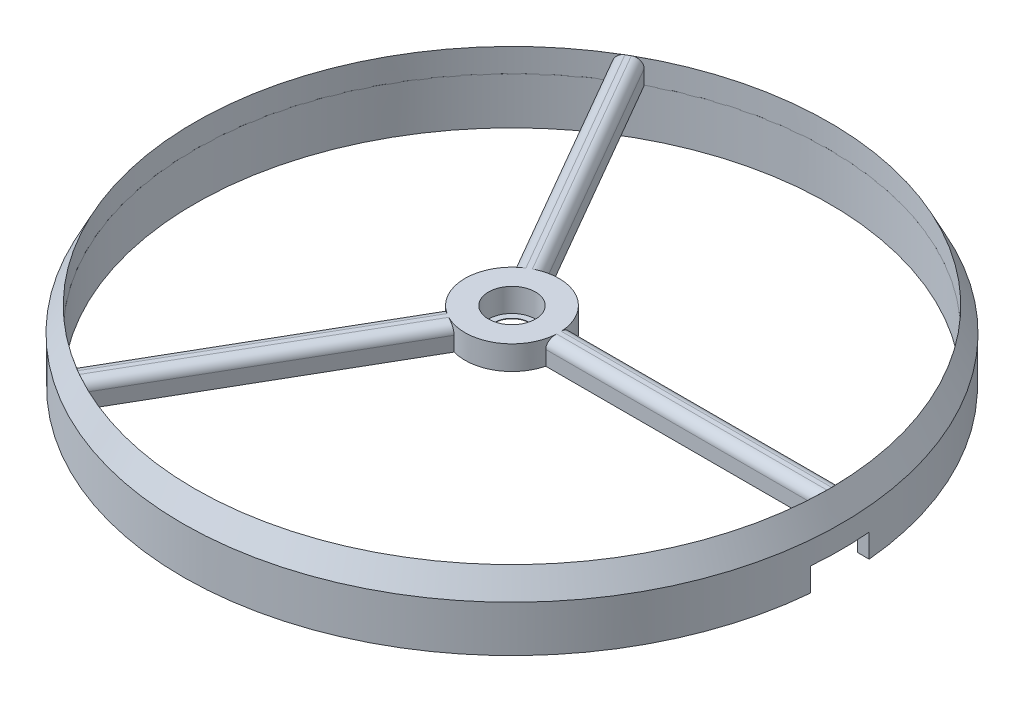
SolidWorks part; units mm, degrees
material "PET"
ref_plane "Front Plane" through (0, 0, 0) normal (0, 0, 1) x (1, 0, 0)
ref_plane "Top Plane" through (0, 0, 0) normal (0, 1, 0) x (1, 0, 0)
ref_plane "Right Plane" through (0, 0, 0) normal (1, 0, 0) x (0, 0, -1)
ref_axis "X-Axis" through (-48.9639, 0, 0) along (1, 0, 0)
ref_axis "Y-Axis" through (0, 10.0012, 0) along (0, -1, 0)
ref_axis "Z-Axis" through (0, 0, -48.9639) along (0, 0, 1)
sketch "Sketch1" plane through (0, 0, 0) normal (0, 1, 0) x (1, 0, 0)
  circle A0 centre (0, 0) radius 44.45
  dimension "D1" = 88.9
extrude "Extrude-Thin1" add sketch "Sketch1" along normal blind 6.35 thin thin type one direction reverse wall 1.5875
sketch "Sketch2" plane through (0, 0, 0) normal (0, -1, 0) x (1, 0, 0)
  circle A0 centre (0, 0) radius 44.45
  dimension "D1" = 88.9
ref_plane "Plane1" through (0, 9.525, 0) normal (0, 1, 0) x (1, 0, 0)
sketch "Sketch8" plane through (0, 9.525, 0) normal (0, 1, 0) x (1, 0, 0)
  circle A0 centre (0, 0) radius 42.8625
  dimension "D1" = 85.725
extrude "Boss-Extrude3" add sketch "Sketch8" against normal blind 3.2385 draft 27 separate body draft outward yes
sketch "Sketch9" plane through (0, 9.525, 0) normal (0, 1, 0) x (1, 0, 0)
  line L1 (6.1484, 1.5875) -> (42.8625, 1.5875)
  line L3 (6.1484, -1.5875) -> (42.8625, -1.5875)
  line L4 (42.8625, 1.5875) -> (42.8625, -1.5875)
  line L5 (6.1656, 1.5191) -> (42.8625, -1.5875) construction
  line L6 (6.1656, -1.5191) -> (42.8625, 1.5875) construction
  line L7 (-1.6994, -6.1184) -> (-20.0564, -37.9138)
  line L8 (-20.0564, -37.9138) -> (-22.8061, -36.3263)
  line L9 (-4.449, -4.5309) -> (-22.8061, -36.3263)
  line L11 (-4.449, 4.5309) -> (-22.8061, 36.3263)
  line L12 (-22.8061, 36.3263) -> (-20.0564, 37.9138)
  line L13 (-1.6994, 6.1184) -> (-20.0564, 37.9138)
  arc A0 (-1.6994, -6.1184) -> (6.1656, -1.5191) centre (0, 0) ccw
  circle A1 centre (0, 0) radius 42.8625 construction
  arc A2 (-4.449, 4.5309) -> (-4.449, -4.5309) centre (0, 0) ccw
  arc A3 (6.1656, 1.5191) -> (-1.6994, 6.1184) centre (0, 0) ccw
  point P3 (24.1101, 0)
  point P11 (0, 0)
  point P12 (6.35, 1.5875)
  point P20 (5.3576, 1.5875)
  circle M14 centre (0, 0) radius 42.8625
  dimension "D1" = 12.7
  dimension "D2" = 3.175
  dimension "D3" = 3
extrude "Cut-Extrude3" cut sketch "Sketch9" against normal blind 4.7625 contours A0 L11 L9 M14 | A0 L1 L13 M14 | A0 L7 L3 M14 region at (12.4069, 9.525, -21.4894) region at (12.4069, 9.525, 21.4894) region at (-24.8138, 9.525, 0)
hole_wizard "CBORE for #00 Binding Head Machine Screw2" positions "Sketch13" profile "Sketch14" counterbore size "#00" standard "ANSI Inch" end condition up to next
sketch "Sketch13" plane through (0, 9.525, 0) normal (0, 1, 0) x (1, 0, 0)
  point P0 (0, 0)
sketch "Sketch14" plane through (0, 9.525, 0) normal (1, 0, 0) x (0, 0, 1)
  line L0 (0, 0) -> (0, 3.2395)
  line L1 (0, 3.2395) -> (2.3813, 3.2395)
  line L3 (2.3813, 3.2395) -> (2.3813, 3.175)
  line L4 (2.3813, 3.175) -> (3.175, 3.175)
  line L5 (3.175, 3.175) -> (3.175, 0)
  line L7 (3.175, 0) -> (0, 0)
  line L11 (0, -6.35) -> (0, 107.95) construction
  dimension "Thru Hole Dia." = 4.7625
  dimension "Thru Hole Depth" = 3.2395
  dimension "C'Bore Dia." = 6.35
  dimension "C'Bore Depth" = 3.175
ref_plane "Plane2" through (43.1173, 0, 0) normal (1, 0, 0) x (0, 0, -1)
sketch "Sketch15" plane through (43.1173, 0, 0) normal (1, 0, 0) x (0, 0, -1)
  line L1 (-3.9687, 3.175) -> (3.9688, 3.175)
  line L2 (-3.9687, 3.175) -> (-3.9687, -3.175)
  line L3 (-3.9687, -3.175) -> (3.9688, -3.175)
  line L4 (3.9688, 3.175) -> (3.9688, -3.175)
  line L5 (-3.9687, 3.175) -> (3.9688, -3.175) construction
  line L6 (-3.9687, -3.175) -> (3.9688, 3.175) construction
  point P0 (0, 0)
  dimension "D1" = 7.9375
  dimension "D2" = 6.35
extrude "Cut-Extrude4" cut sketch "Sketch15" along normal mid plane 6.35
fillet "Fillet4" radius 1.27 2 edges at (-10.8705, 9.525, -22.0033) (-13.6202, 9.525, -20.4158)
fillet "Fillet5" radius 1.27 2 edges at (-10.8705, 9.525, 22.0033) (-13.6202, 9.525, 20.4158)
fillet "Fillet6" radius 1.27 2 edges at (24.4907, 9.525, -1.5875) (24.4907, 9.525, 1.5875)
